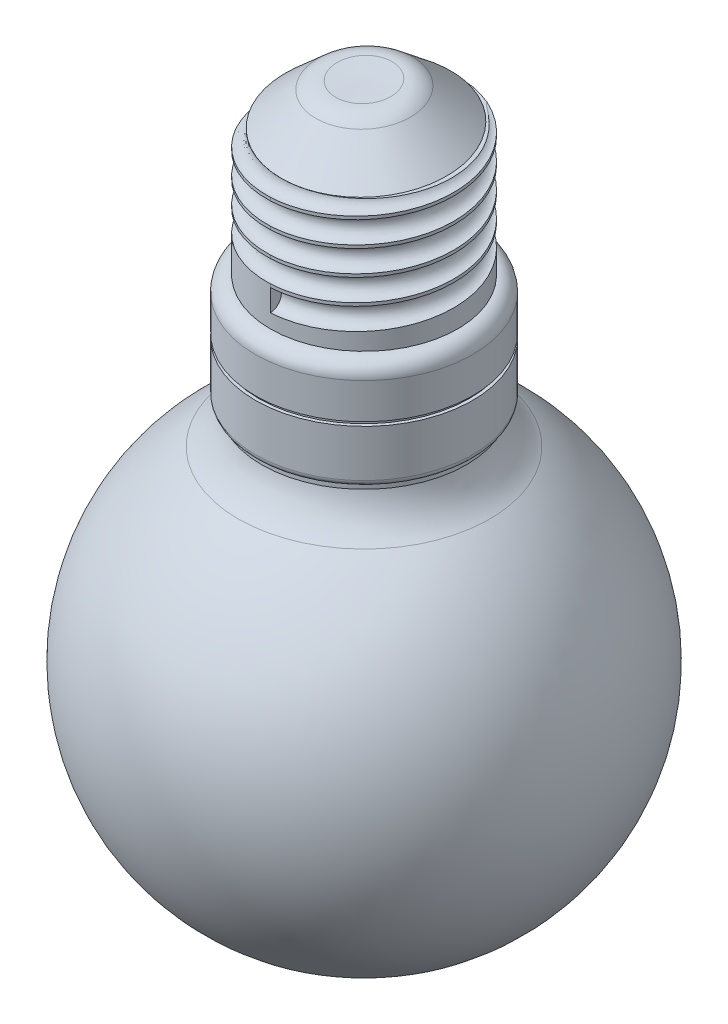
SolidWorks part; units mm, degrees
ref_plane "Front Plane" through (0, 0, 0) normal (0, 0, 1) x (1, 0, 0)
ref_plane "Top Plane" through (0, 0, 0) normal (0, 1, 0) x (1, 0, 0)
ref_plane "Right Plane" through (0, 0, 0) normal (1, 0, 0) x (0, 0, -1)
sketch "Sketch1" plane through (0, 0, 0) normal (0, 0, 1) x (1, 0, 0)
  line L0 (0, 102.8673) -> (0, -108.2742) construction
sketch "Sketch2" plane through (0, 0, 0) normal (0, 0, 1) x (1, 0, 0)
  line L0 (0, 66.6407) -> (-300, 66.6407)
  line L1 (0, 102.8673) -> (0, -108.2742) construction
  line L2 (-300, 66.6407) -> (-300, -333.3593)
  line L9 (0.325, -137.6873) -> (0, 66.6407)
  line L10 (-347.5913, -380.9506) -> (-347.5913, -495.0113)
  line L11 (-347.5913, -495.0113) -> (-337.2, -495.0113)
  line L12 (-337.2, -495.0113) -> (-337.2, -507.8009)
  line L13 (-337.2, -507.8009) -> (-347.5913, -507.8009)
  line L14 (-347.5913, -507.8009) -> (-347.5913, -658.0865)
  line L15 (-327.1647, -678.513) -> (-327.1647, -696.7833)
  line L16 (0, 445.8633) -> (0, -2415.8252) construction
  line L17 (0, -2122.2361) -> (0, 66.6407)
  arc A0 (-300, -333.3593) -> (-347.5913, -380.9506) centre (-300, -380.9506) ccw
  arc A1 (-347.5913, -658.0865) -> (-327.1647, -678.513) centre (-327.1647, -658.0865) ccw
  arc A2 (-402.8131, -808.8708) -> (0, -2122.2361) centre (0, -1403.7814) ccw
  spline S0 degree 3 poles (-327.1647, -696.7833) (-338.223, -744.8482) (-363.4391, -782.2107) (-402.8131, -808.8708) knots 0 0 0 0 1 1 1 1
  dimension "D1" = 400
  dimension "D2" = 300
revolve "Revolve2" add sketch "Sketch2" angle 360 about L16 region at (-271.8659, -1151.6683, 0)
sketch "Sketch4" plane through (0, 66.6407, 0) normal (0, 1, 0) x (1, 0, 0)
  circle A0 centre (0, 0) radius 300 construction
  circle A1 centre (0, 0) radius 300
sketch "Sketch8" plane through (0, 0, 0) normal (1, 0, 0) x (0, 0, -1)
sketch "Sketch11" plane through (0, 66.6407, 0) normal (0, 1, 0) x (1, 0, 0)
  circle A0 centre (0, 0) radius 300 construction
  circle A1 centre (0, 0) radius 300
curve "Helix/Spiral2" pitch 80 height 320 radius 300 centre (0, 66.6407, 0) axis (0, -1, 0) start towards (0, 0, 1)
sketch "Sketch12" plane through (0, 0, 0) normal (1, 0, 0) x (0, 0, -1)
  line L0 (-300, 66.6407) -> (-300, -333.3593) construction
  circle A0 centre (-300, -253.1816) radius 35
  dimension "D1" = 70
sweep "Cut-Sweep2" cut profiles "Sketch12" path "Helix/Spiral2" align with end faces yes
sketch "Sketch13" plane through (0, 0, 0) normal (1, 0, 0) x (0, 0, -1)
  line L0 (278.7433, 66.6407) -> (-265.0005, 66.6407) construction
  line L1 (-264.996, 66.6407) -> (-154.2543, 177.3824)
  line L2 (-90.3223, 203.8639) -> (0, 203.8639)
  line L3 (0, 203.8639) -> (6.8714, 66.6407)
  line L4 (6.8714, 66.6407) -> (-264.996, 66.6407)
  arc A0 (-154.2543, 177.3824) -> (-90.3223, 203.8639) centre (-90.3223, 113.4504) cw
revolve "Revolve3" add sketch "Sketch13" angle 360 about L3
